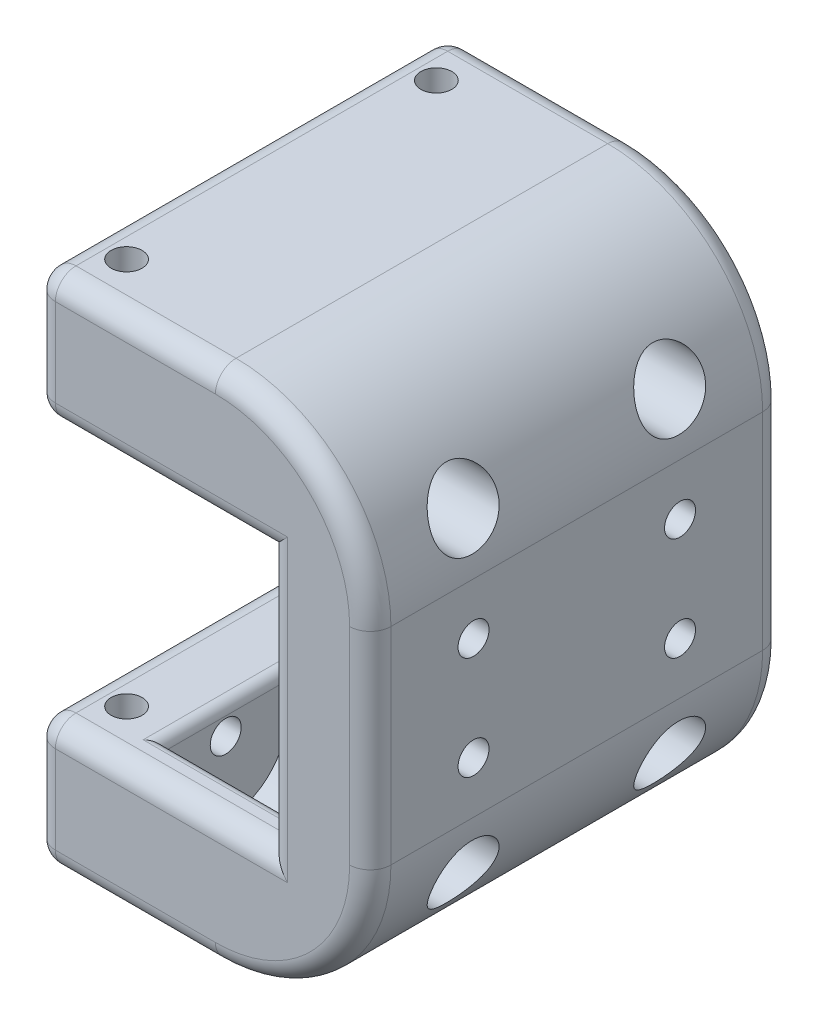
SolidWorks part; units mm, degrees
ref_plane "Front Plane" through (0, 0, 0) normal (0, 0, 1) x (1, 0, 0)
ref_plane "Top Plane" through (0, 0, 0) normal (0, 1, 0) x (1, 0, 0)
ref_plane "Right Plane" through (0, 0, 0) normal (1, 0, 0) x (0, 0, -1)
sketch "Sketch1" plane through (0, 0, 0) normal (0, 0, 1) x (1, 0, 0)
  line L0 (0, 0) -> (0, 63.5)
  line L1 (0, 63.5) -> (-41.275, 63.5)
  line L2 (-41.275, 63.5) -> (-41.275, 47.625)
  line L3 (-41.275, 47.625) -> (-12.7, 47.625)
  line L4 (-12.7, 47.625) -> (-12.7, 15.875)
  line L5 (-12.7, 15.875) -> (-41.275, 15.875)
  line L6 (-41.275, 15.875) -> (-41.275, 0)
  line L7 (-41.275, 0) -> (0, 0)
  point P9 (-26.8025, -1.5583)
  point P10 (-27.0102, 0)
  point P11 (-50.8941, 50.8)
  point P12 (-37.5671, -6.35)
  point P13 (-37.5671, 6.35)
  point P14 (-38.0896, -0.8918)
  dimension "D1" = 31.75
  dimension "D2" = 41.275
  dimension "D3" = 12.7
  dimension "D5" = 15.875
extrude "Boss-Extrude1" add sketch "Sketch1" along normal blind 50.8
ref_plane "Plane1" through (0, 0, 25.4) normal (0, 0, -1) x (-1, 0, 0)
ref_plane "Plane2" through (0, 31.75, 0) normal (0, 1, 0) x (1, 0, 0)
ref_plane "Plane3" through (-15.24, 0, 0) normal (-1, 0, 0) x (0, 0, 1)
sketch "Sketch2" plane through (0, 63.5, 0) normal (0, 1, 0) x (1, 0, 0)
  line L2 (0, 0) -> (-41.275, 0) construction
  line L3 (0, -50.8) -> (0, 0) construction
  circle A0 centre (-36.322, -44.45) radius 1.905
  circle A1 centre (-36.322, -6.35) radius 1.905
  point P8 (0, 0)
  dimension "D1" = 3.81
  dimension "D2" = 6.35
  dimension "D4" = 36.322
  dimension "D3" = 44.45
extrude "Cut-Extrude1" cut sketch "Sketch2" against normal through all
sketch "Sketch5" plane through (-15.24, 0, 0) normal (-1, 0, 0) x (0, 0, 1)
  line L0 (50.8, 0) -> (0, 0) construction
  line L1 (0, 15.875) -> (0, 0) construction
  line L2 (5.08, 11.1125) -> (5.08, 15.875)
  line L3 (50.8, 15.875) -> (0, 15.875) construction
  line L4 (5.08, 15.875) -> (20.32, 15.875)
  line L5 (20.32, 15.875) -> (20.32, 11.1125)
  arc A0 (5.08, 11.1125) -> (20.32, 11.1125) centre (12.7, 11.1125) ccw
  dimension "D1" = 15.24
  dimension "D3" = 12.7
  dimension "D2" = 11.1125
extrude "Cut-Extrude2" cut sketch "Sketch5" along normal blind 15.24
sketch "Sketch7" plane through (0, 0, 0) normal (-1, 0, 0) x (0, 0, 1)
  line L0 (0, 47.625) -> (0, 15.875) construction
  line L1 (50.8, 0) -> (0, 0) construction
  circle A0 centre (12.7, 12.3825) radius 2.286
  dimension "D3" = 4.572
  dimension "D1" = 12.7
  dimension "D2" = 12.3825
extrude "Cut-Extrude3" cut sketch "Sketch7" along normal up to surface (15.24 mm away) and the other way through all up to face at (-15.24, 11.5888, 12.7)
sketch "Sketch8" plane through (0, 0, 0) normal (1, 0, 0) x (0, 0, -1)
  circle A4 centre (-12.7, 12.3825) radius 4.1275
  dimension "D1" = 8.255
extrude "Cut-Extrude4" cut sketch "Sketch8" against normal blind 9.525 and the other way through all
sketch "Sketch12" plane through (0, 0, 0) normal (1, 0, 0) x (0, 0, -1)
  line L0 (-50.8, 0) -> (0, 0) construction
  line L1 (0, 0) -> (0, 63.5) construction
  circle A0 centre (-12.7, 25.4) radius 1.905
  dimension "D1" = 3.81
  dimension "D3" = 12.7
  dimension "D2" = 25.4
extrude "Cut-Extrude8" cut sketch "Sketch12" against normal blind 9.525
sketch "Sketch13" plane through (-12.7, 0, 0) normal (-1, 0, 0) x (0, 0, 1)
  line L0 (50.8, 0) -> (0, 0) construction
  line L1 (0, 47.625) -> (0, 15.875) construction
  circle A0 centre (6.35, 31.75) radius 1.905
  dimension "D1" = 31.75
  dimension "D2" = 6.35
  dimension "D3" = 3.81
extrude "Cut-Extrude9" cut sketch "Sketch13" against normal blind 9.525
sketch "Sketch14" plane through (-41.275, 0, 0) normal (-1, 0, 0) x (0, 0, 1)
  line L0 (0, 15.875) -> (0, 0) construction
  line L1 (50.8, 0) -> (0, 0) construction
  circle A0 centre (12.7, 12.446) radius 1.905
  dimension "D1" = 3.81
  dimension "D2" = 12.7
  dimension "D3" = 12.446
extrude "Cut-Extrude10" cut sketch "Sketch14" against normal up to surface (10.795 mm away) up to face at (-30.48, 11.5888, 12.7)
mirror "Mirror3" about plane through (0, 0, 25.4) normal (0, 0, -1) of "Cut-Extrude10", "Cut-Extrude2", "Cut-Extrude9", "Cut-Extrude8", "Cut-Extrude4", "Cut-Extrude3"
mirror "Mirror4" about plane through (0, 31.75, 0) normal (0, 1, 0) of "Mirror3", "Cut-Extrude8"
fillet "Fillet3" radius 19.05 2 edges at (0, 0, 25.4) (0, 63.5, 25.4)
fillet "Fillet4" radius 2.54 24 edges at (-30.1625, 63.5, 50.8) (-5.5796, 57.9204, 50.8) (0, 31.75, 50.8) (-5.5796, 5.5796, 50.8) (-30.1625, 63.5, 0) (-5.5796, 57.9204, 0) (0, 31.75, 0) (-5.5796, 5.5796, 0) (-26.9875, 47.625, 50.8) (-30.1625, 0, 50.8) (-26.9875, 15.875, 50.8) (-12.7, 31.75, 50.8) (-26.9875, 47.625, 0) (-12.7, 31.75, 0) (-26.9875, 15.875, 0) (-30.1625, 0, 0) (-41.275, 7.9375, 50.8) (-41.275, 15.875, 25.4) (-41.275, 7.9375, 0) (-41.275, 0, 25.4) (-41.275, 55.5625, 50.8) (-41.275, 63.5, 25.4) (-41.275, 55.5625, 0) (-41.275, 47.625, 25.4)
fillet "Fillet5" radius 1.27 16 edges at (-30.48, 47.625, 38.1) (-22.86, 47.625, 45.72) (-15.24, 47.625, 38.1) (-22.86, 47.625, 30.48) (-22.86, 47.625, 20.32) (-30.48, 47.625, 12.7) (-22.86, 47.625, 5.08) (-15.24, 47.625, 12.7) (-22.86, 15.875, 45.72) (-30.48, 15.875, 38.1) (-22.86, 15.875, 30.48) (-15.24, 15.875, 38.1) (-15.24, 15.875, 12.7) (-22.86, 15.875, 5.08) (-30.48, 15.875, 12.7) (-22.86, 15.875, 20.32)
